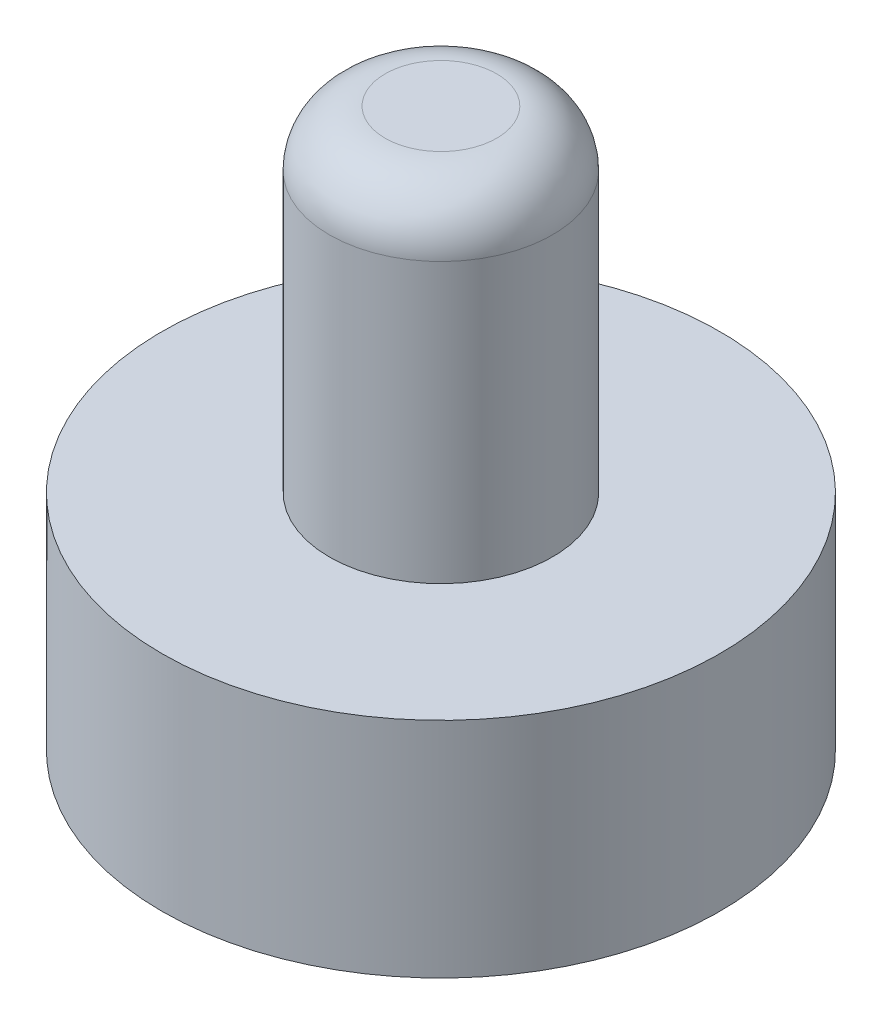
SolidWorks part; units mm, degrees
ref_plane "前视基准面" through (0, 0, 0) normal (0, 0, 1) x (1, 0, 0)
ref_plane "上视基准面" through (0, 0, 0) normal (0, 1, 0) x (1, 0, 0)
ref_plane "右视基准面" through (0, 0, 0) normal (1, 0, 0) x (0, 0, -1)
other "Configuration Table"
sketch "草图1" plane through (0, 0, 0) normal (0, 1, 0) x (1, 0, 0)
  circle A0 centre (0, 0) radius 2.5
  dimension "D1" = 5
extrude "凸台-拉伸1" add sketch "草图1" along normal blind 2
sketch "草图2" plane through (0, 2, 0) normal (0, 1, 0) x (1, 0, 0)
  circle A0 centre (0, 0) radius 1
  dimension "D1" = 2
extrude "凸台-拉伸2" add sketch "草图2" along normal blind 3
fillet "圆角1" radius 0.5 1 edges at (0, 5, 1)
